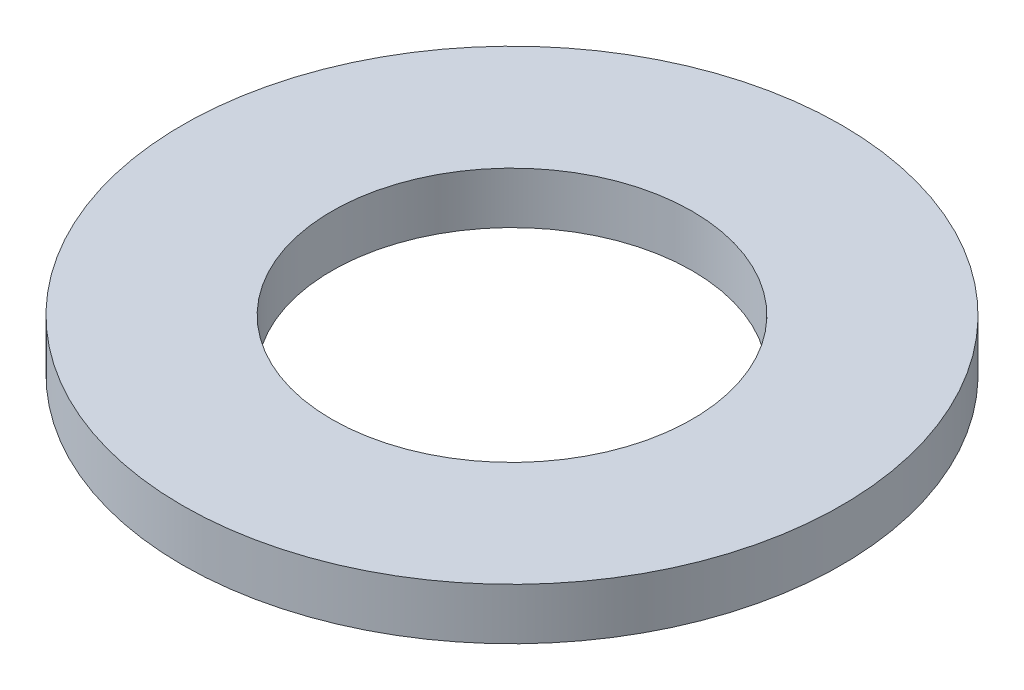
SolidWorks part; units mm, degrees
material "HYPALON"
ref_plane "Front Plane" through (0, 0, 0) normal (0, 0, 1) x (1, 0, 0)
ref_plane "Top Plane" through (0, 0, 0) normal (0, 1, 0) x (1, 0, 0)
ref_plane "Right Plane" through (0, 0, 0) normal (1, 0, 0) x (0, 0, -1)
sketch "Szkic1" plane through (0, 0, 0) normal (0, 0, 1) x (1, 0, 0)
  line L0 (0, 0) -> (-64, 0)
  line L1 (-64, 0) -> (-64, 10)
  line L2 (-64, 10) -> (-35, 10)
  line L3 (-35, 10) -> (-35, 0)
  line L4 (0, 0) -> (0, 23.5461)
  dimension "D1" = 64
  dimension "D2" = 10
  dimension "D3" = 35
revolve "Obrót1" add sketch "Szkic1" angle 360 about L4 region at (-49.5, 5, 0)
